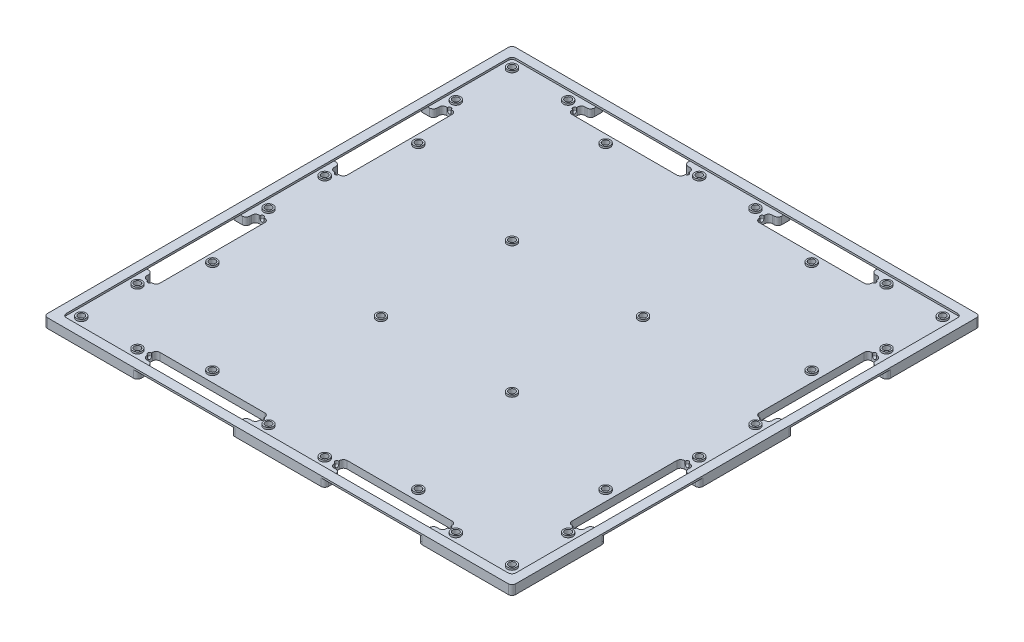
SolidWorks part; units mm, degrees
material "99.5% Aluminum Oxide"
ref_plane "Front Plane" through (0, 0, 0) normal (0, 0, 1) x (1, 0, 0)
ref_plane "Top Plane" through (0, 0, 0) normal (0, 1, 0) x (1, 0, 0)
ref_plane "Right Plane" through (0, 0, 0) normal (1, 0, 0) x (0, 0, -1)
sketch "Sketch1" plane through (0, 0, 0) normal (0, 1, 0) x (1, 0, 0)
  line L1 (-125, -125) -> (125, -125)
  line L2 (-125, -125) -> (-125, 125)
  line L3 (-125, 125) -> (125, 125)
  line L4 (125, -125) -> (125, 125)
  line L5 (-125, -125) -> (125, 125) construction
  line L6 (-125, 125) -> (125, -125) construction
  point P0 (0, 0)
  dimension "D1" = 250
extrude "Boss-Extrude1" add sketch "Sketch1" along normal mid plane 4
sketch "Sketch2" plane through (0, 2, 0) normal (0, 1, 0) x (1, 0, 0)
  line L0 (-125, 125) -> (-125, -125) construction
  line L1 (-120, -120) -> (120, -120)
  line L2 (-120, -120) -> (-120, 120)
  line L3 (-120, 120) -> (120, 120)
  line L4 (120, -120) -> (120, 120)
  line L5 (-120, -120) -> (120, 120) construction
  line L6 (-120, 120) -> (120, -120) construction
  point P0 (0, 0)
  dimension "D1" = 5
extrude "Cut-Extrude1" cut sketch "Sketch2" against normal blind 1
sketch "Sketch9" plane through (0, 1, 0) normal (0, 1, 0) x (1, 0, 0)
  line L0 (125, 125) -> (75, 125) construction
  line L1 (125, 125) -> (-125, 125) construction
  line L2 (25, 125) -> (-25, 125) construction
  line L3 (-125, 125) -> (-75, 125) construction
  line L4 (75, 117) -> (80, 117)
  line L5 (75, 125) -> (25, 125)
  line L6 (75, 125) -> (75, 117)
  line L8 (25, 125) -> (25, 117)
  line L9 (-25, 125) -> (-75, 125)
  line L10 (-25, 125) -> (-25, 117)
  line L12 (-75, 125) -> (-75, 117)
  line L13 (125, -125) -> (125, 125) construction
  line L32 (80, 117) -> (80, 110)
  line L33 (80, 110) -> (20, 110)
  line L34 (20, 110) -> (20, 117)
  line L35 (20, 117) -> (25, 117)
  line L36 (-25, 117) -> (-20, 117)
  line L37 (-20, 117) -> (-20, 110)
  line L38 (-20, 110) -> (-80, 110)
  line L39 (-80, 110) -> (-80, 117)
  line L40 (-80, 117) -> (-75, 117)
  dimension "D1" = 50
  dimension "D2" = 50
  dimension "D3" = 5
  dimension "D4" = 7
  dimension "D5" = 15
extrude "Cut-Extrude2" cut sketch "Sketch9" against normal through all
sketch "Sketch12" plane through (80, 0, 0) normal (-1, 0, 0) x (0, 0, 1)
  line L0 (-113.5, 1) -> (-113.5, -1.5)
  line L1 (-110, 1) -> (-117, 1) construction
  line L2 (-112.5, -0.5) -> (-112.5, 1)
  line L3 (-112.5, 1) -> (-113.5, 1)
  line L4 (-113.5, 1) -> (-113.5, -2) construction
  line L5 (-110, -2) -> (-117, -2) construction
  arc A0 (-113.5, -1.5) -> (-112.5, -0.5) centre (-113.5, -0.5) ccw
  point P7 (-113.5, -0.5)
  dimension "D1" = 1
revolve "Cut-Revolve1" cut sketch "Sketch12" angle 360 about L4
ref_plane "Plane1" through (50, 0, 0) normal (1, 0, 0) x (0, 0, -1)
mirror "Mirror1" about plane through (50, 0, 0) normal (1, 0, 0) of "Cut-Revolve1"
mirror "Mirror2" about plane through (0, 0, 0) normal (1, 0, 0) of "Cut-Revolve1", "Mirror1"
ref_axis "Center_Axis" through (0, -22.0017, 0) along (0, 1, 0)
pattern_circular "CirPattern1" count 4 over 360 about axis through (0, -22.0017, 0) along (0, 1, 0) of "Mirror2", "Cut-Extrude2", "Cut-Revolve1", "Mirror1"
sketch "Sketch14" plane through (0, 1, 0) normal (0, 1, 0) x (1, 0, 0)
  line L0 (-120, 120) -> (-120, -120) construction
  line L1 (-110, 120) -> (-110, -120) construction
  line L2 (-100, 120) -> (-100, -120) construction
  line L3 (-90, 120) -> (-90, -120) construction
  line L4 (-80, 120) -> (-80, -120) construction
  line L5 (-70, 120) -> (-70, -120) construction
  line L6 (-60, 120) -> (-60, -120) construction
  line L7 (-50, 120) -> (-50, -120) construction
  line L8 (-40, 120) -> (-40, -120) construction
  line L9 (-30, 120) -> (-30, -120) construction
  line L10 (-20, 120) -> (-20, -120) construction
  line L11 (-10, 120) -> (-10, -120) construction
  line L12 (0, 120) -> (0, -120) construction
  line L13 (10, 120) -> (10, -120) construction
  line L14 (20, 120) -> (20, -120) construction
  line L15 (30, 120) -> (30, -120) construction
  line L16 (40, 120) -> (40, -120) construction
  line L17 (50, 120) -> (50, -120) construction
  line L18 (60, 120) -> (60, -120) construction
  line L19 (70, 120) -> (70, -120) construction
  line L20 (80, 120) -> (80, -120) construction
  line L21 (90, 120) -> (90, -120) construction
  line L22 (100, 120) -> (100, -120) construction
  line L23 (110, 120) -> (110, -120) construction
  line L24 (120, 120) -> (120, -120) construction
  line L25 (-120, 120) -> (-110, 120) construction
  line L26 (-15, -115) -> (-15, -120) construction
  line L27 (-25, -120) -> (25, -120) construction
  line L28 (-125, 125) -> (-125, -125) construction
  line L29 (-85, -120) -> (-85, -115) construction
  line L30 (-120, -120) -> (-75, -120) construction
  line L31 (-115, -120) -> (-115, -115) construction
  line L32 (-120, -120) -> (120, -120) construction
  line L33 (-55, -110) -> (-55, -105) construction
  line L34 (-20, -110) -> (-80, -110) construction
  line L35 (-125, -125) -> (125, -125) construction
  line L36 (0, 0) -> (15, -115) construction
  line L37 (35, 35) -> (-35, 35) construction
  line L38 (35, 35) -> (35, -35) construction
  line L39 (35, -35) -> (-35, -35) construction
  line L40 (-35, 35) -> (-35, -35) construction
  line L41 (35, 35) -> (-35, -35) construction
  line L42 (35, -35) -> (-35, 35) construction
  line L43 (115, -117.5) -> (115, -120) construction
  line L44 (75, -120) -> (120, -120) construction
  circle A2 centre (-15, -115) radius 2.5
  circle A3 centre (-85, -115) radius 2.5
  circle A4 centre (-115, -115) radius 2.5
  circle A5 centre (-55, -105) radius 2.5
  circle A6 centre (-35, 35) radius 2.5
  circle A7 centre (-35, -35) radius 2.5
  circle A8 centre (35, -35) radius 2.5
  circle A9 centre (35, 35) radius 2.5
  circle A10 centre (15, -115) radius 2.5
  circle A11 centre (55, -105) radius 2.5
  circle A12 centre (85, -115) radius 2.5
  circle A13 centre (-115, 115) radius 2.5
  circle A14 centre (-115, 85) radius 2.5
  circle A15 centre (-105, 55) radius 2.5
  circle A16 centre (-115, 15) radius 2.5
  circle A17 centre (-115, -15) radius 2.5
  circle A18 centre (-105, -55) radius 2.5
  circle A19 centre (-115, -85) radius 2.5
  circle A20 centre (115, 115) radius 2.5
  circle A21 centre (85, 115) radius 2.5
  circle A22 centre (55, 105) radius 2.5
  circle A23 centre (15, 115) radius 2.5
  circle A24 centre (-15, 115) radius 2.5
  circle A25 centre (-55, 105) radius 2.5
  circle A26 centre (-85, 115) radius 2.5
  circle A27 centre (115, -115) radius 2.5
  circle A28 centre (115, -85) radius 2.5
  circle A29 centre (105, -55) radius 2.5
  circle A30 centre (115, -15) radius 2.5
  circle A31 centre (115, 15) radius 2.5
  circle A32 centre (105, 55) radius 2.5
  circle A33 centre (115, 85) radius 2.5
  arc A34 (120, -118) -> (118, -120) centre (118, -118) cw construction
  point P78 (0, 0)
  dimension "D5" = 5
  dimension "D14" = 2
  dimension "D2" = 10
  dimension "D3" = 110
  dimension "D4" = 5
  dimension "D6" = 40
  dimension "D7" = 10
  dimension "D8" = 20
  dimension "D9" = 70
  dimension "D10" = 90
  dimension "D12" = 115.9741
  dimension "D13" = 2.5
  dimension "D1" = 25
  dimension "D11" = 4
extrude "Boss-Extrude2" add sketch "Sketch14" along normal up to surface (1 mm away) up to face at (0, 2, 0)
sketch "Sketch19" plane through (0, -2, 0) normal (0, -1, 0) x (1, 0, 0)
  line L0 (-110, 55) -> (-105, 55) construction
  line L1 (-100, -100) -> (100, -100)
  line L2 (-100, -100) -> (-100, 100)
  line L3 (-100, 100) -> (100, 100)
  line L4 (100, -100) -> (100, 100)
  line L5 (-100, -100) -> (100, 100) construction
  line L6 (-100, 100) -> (100, -100) construction
  line L7 (-105, 55) -> (-100, 55) construction
  line L68 (117, -25) -> (125, -25)
  line L69 (125, -25) -> (125, 25)
  line L70 (125, 25) -> (117, 25)
  line L71 (117, 25) -> (117, 20)
  line L72 (117, 20) -> (110, 20)
  line L73 (110, 20) -> (110, 80)
  line L74 (110, 80) -> (117, 80)
  line L75 (117, 80) -> (117, 75)
  line L76 (117, 75) -> (125, 75)
  line L77 (125, 75) -> (125, 125)
  line L78 (125, 125) -> (75, 125)
  line L79 (75, 125) -> (75, 117)
  line L80 (75, 117) -> (80, 117)
  line L81 (80, 117) -> (80, 110)
  line L82 (80, 110) -> (20, 110)
  line L83 (20, 110) -> (20, 117)
  line L84 (20, 117) -> (25, 117)
  line L85 (25, 117) -> (25, 125)
  line L86 (25, 125) -> (-25, 125)
  line L87 (-25, 125) -> (-25, 117)
  line L88 (-25, 117) -> (-20, 117)
  line L89 (-20, 117) -> (-20, 110)
  line L90 (-20, 110) -> (-80, 110)
  line L91 (-80, 110) -> (-80, 117)
  line L92 (-80, 117) -> (-75, 117)
  line L93 (-75, 117) -> (-75, 125)
  line L94 (-75, 125) -> (-125, 125)
  line L95 (-125, 125) -> (-125, 75)
  line L96 (-125, 75) -> (-117, 75)
  line L97 (-117, 75) -> (-117, 80)
  line L98 (-117, 80) -> (-110, 80)
  line L99 (-110, 80) -> (-110, 20)
  line L100 (-110, 20) -> (-117, 20)
  line L101 (-117, 20) -> (-117, 25)
  line L102 (-117, 25) -> (-125, 25)
  line L103 (-125, 25) -> (-125, -25)
  line L104 (-125, -25) -> (-117, -25)
  line L105 (-117, -25) -> (-117, -20)
  line L106 (-117, -20) -> (-110, -20)
  line L107 (-110, -20) -> (-110, -80)
  line L108 (-110, -80) -> (-117, -80)
  line L109 (-117, -80) -> (-117, -75)
  line L110 (-117, -75) -> (-125, -75)
  line L111 (-125, -75) -> (-125, -125)
  line L112 (-125, -125) -> (-75, -125)
  line L113 (-75, -125) -> (-75, -117)
  line L114 (-75, -117) -> (-80, -117)
  line L115 (-80, -117) -> (-80, -110)
  line L116 (-80, -110) -> (-20, -110)
  line L117 (-20, -110) -> (-20, -117)
  line L118 (-20, -117) -> (-25, -117)
  line L119 (-25, -117) -> (-25, -125)
  line L120 (-25, -125) -> (25, -125)
  line L121 (25, -125) -> (25, -117)
  line L122 (25, -117) -> (20, -117)
  line L123 (20, -117) -> (20, -110)
  line L124 (20, -110) -> (80, -110)
  line L125 (80, -110) -> (80, -117)
  line L126 (80, -117) -> (75, -117)
  line L127 (75, -117) -> (75, -125)
  line L128 (75, -125) -> (125, -125)
  line L129 (125, -125) -> (125, -75)
  line L130 (125, -75) -> (117, -75)
  line L131 (117, -75) -> (117, -80)
  line L132 (117, -80) -> (110, -80)
  line L133 (110, -80) -> (110, -20)
  line L134 (110, -20) -> (117, -20)
  line L135 (117, -20) -> (117, -25)
  line L136 (117, -25) -> (125, -25)
  line L137 (125, -25) -> (125, 25)
  line L138 (125, 25) -> (117, 25)
  line L139 (117, 25) -> (117, 20)
  line L140 (117, 20) -> (110, 20)
  line L141 (110, 20) -> (110, 80)
  line L142 (110, 80) -> (117, 80)
  line L143 (117, 80) -> (117, 75)
  line L144 (117, 75) -> (125, 75)
  line L145 (125, 75) -> (125, 125)
  line L146 (125, 125) -> (75, 125)
  line L147 (75, 125) -> (75, 117)
  line L148 (75, 117) -> (80, 117)
  line L149 (80, 117) -> (80, 110)
  line L150 (80, 110) -> (20, 110)
  line L151 (20, 110) -> (20, 117)
  line L152 (20, 117) -> (25, 117)
  line L153 (25, 117) -> (25, 125)
  line L154 (25, 125) -> (-25, 125)
  line L155 (-25, 125) -> (-25, 117)
  line L156 (-25, 117) -> (-20, 117)
  line L157 (-20, 117) -> (-20, 110)
  line L158 (-20, 110) -> (-80, 110)
  line L159 (-80, 110) -> (-80, 117)
  line L160 (-80, 117) -> (-75, 117)
  line L161 (-75, 117) -> (-75, 125)
  line L162 (-75, 125) -> (-125, 125)
  line L163 (-125, 125) -> (-125, 75)
  line L164 (-125, 75) -> (-117, 75)
  line L165 (-117, 75) -> (-117, 80)
  line L166 (-117, 80) -> (-110, 80)
  line L167 (-110, 80) -> (-110, 20)
  line L168 (-110, 20) -> (-117, 20)
  line L169 (-117, 20) -> (-117, 25)
  line L170 (-117, 25) -> (-125, 25)
  line L171 (-125, 25) -> (-125, -25)
  line L172 (-125, -25) -> (-117, -25)
  line L173 (-117, -25) -> (-117, -20)
  line L174 (-117, -20) -> (-110, -20)
  line L175 (-110, -20) -> (-110, -80)
  line L176 (-110, -80) -> (-117, -80)
  line L177 (-117, -80) -> (-117, -75)
  line L178 (-117, -75) -> (-125, -75)
  line L179 (-125, -75) -> (-125, -125)
  line L180 (-125, -125) -> (-75, -125)
  line L181 (-75, -125) -> (-75, -117)
  line L182 (-75, -117) -> (-80, -117)
  line L183 (-80, -117) -> (-80, -110)
  line L184 (-80, -110) -> (-20, -110)
  line L185 (-20, -110) -> (-20, -117)
  line L186 (-20, -117) -> (-25, -117)
  line L187 (-25, -117) -> (-25, -125)
  line L188 (-25, -125) -> (25, -125)
  line L189 (25, -125) -> (25, -117)
  line L190 (25, -117) -> (20, -117)
  line L191 (20, -117) -> (20, -110)
  line L192 (20, -110) -> (80, -110)
  line L193 (80, -110) -> (80, -117)
  line L194 (80, -117) -> (75, -117)
  line L195 (75, -117) -> (75, -125)
  line L196 (75, -125) -> (125, -125)
  line L197 (125, -125) -> (125, -75)
  line L198 (125, -75) -> (117, -75)
  line L199 (117, -75) -> (117, -80)
  line L200 (117, -80) -> (110, -80)
  line L201 (110, -80) -> (110, -20)
  line L202 (110, -20) -> (117, -20)
  line L203 (117, -20) -> (117, -25)
  circle A1 centre (-105, 55) radius 2.5
  circle A2 centre (-105, 55) radius 2.5 construction
  point P2 (0, 0)
  dimension "D3" = 10
  dimension "D1" = 0
  dimension "D2" = 0
extrude "Boss-Extrude3" add sketch "Sketch19" along normal blind 1
sketch "Sketch20" plane through (0, -2, 0) normal (0, -1, 0) x (1, 0, 0)
  line L0 (33.3771, -47.8109) -> (58.094, -5)
  line L37 (-49.4338, 0) -> (-24.7169, -42.8109)
  line L38 (-24.7169, -42.8109) -> (24.7169, -42.8109)
  line L39 (24.7169, -42.8109) -> (49.4338, 0)
  line L40 (49.4338, 0) -> (24.7169, 42.8109)
  line L41 (24.7169, 42.8109) -> (-24.7169, 42.8109)
  line L42 (-24.7169, 42.8109) -> (-49.4338, 0)
  line L43 (58.094, -5) -> (100, -5)
  line L44 (100, -100) -> (100, 100) construction
  line L45 (33.3771, -47.8109) -> (63.5085, -100)
  line L46 (-100, -100) -> (100, -100) construction
  line L47 (100, -100) -> (100, 100) construction
  line L48 (-100, -100) -> (100, -100) construction
  line L49 (49.4338, 0) -> (-49950.5662, 0) construction
  line L50 (51.9615, -100) -> (24.7169, -52.8109)
  line L51 (24.7169, -52.8109) -> (-24.7169, -52.8109)
  line L53 (-24.7169, -52.8109) -> (-51.9615, -100)
  line L54 (0, 0) -> (0, -50000) construction
  line L55 (-33.3771, -47.8109) -> (-63.5085, -100)
  line L56 (-33.3771, -47.8109) -> (-58.094, -5)
  line L57 (-58.094, -5) -> (-100, -5)
  line L58 (-33.3771, 47.8109) -> (-63.5085, 100)
  line L59 (-58.094, 5) -> (-100, 5)
  line L60 (-33.3771, 47.8109) -> (-58.094, 5)
  line L61 (24.7169, 52.8109) -> (-24.7169, 52.8109)
  line L62 (-24.7169, 52.8109) -> (-51.9615, 100)
  line L63 (51.9615, 100) -> (24.7169, 52.8109)
  line L64 (33.3771, 47.8109) -> (63.5085, 100)
  line L65 (33.3771, 47.8109) -> (58.094, 5)
  line L66 (58.094, 5) -> (100, 5)
  line L67 (63.5085, -100) -> (51.9615, -100)
  line L68 (-51.9615, -100) -> (-63.5085, -100)
  line L69 (-100, -5) -> (-100, 5)
  line L70 (-63.5085, 100) -> (-51.9615, 100)
  line L71 (51.9615, 100) -> (63.5085, 100)
  line L72 (100, -5) -> (100, 5)
  circle A0 centre (35, -35) radius 2.5 construction
  circle A1 centre (35, 35) radius 2.5 construction
  circle A2 centre (-35, -35) radius 2.5 construction
  circle A3 centre (-35, 35) radius 2.5 construction
  circle A4 centre (35, -35) radius 2.5 construction
  circle A5 centre (35, 35) radius 2.5 construction
  circle A6 centre (-35, -35) radius 2.5 construction
  circle A7 centre (-35, 35) radius 2.5 construction
  circle A8 centre (0, 0) radius 42.8109 construction
  arc A9 (100, -8.6024) -> (100, -87.0194) centre (82.8109, -47.8109) ccw construction
  arc A10 (42.5864, -100) -> (-42.5864, -100) centre (0, -95.6218) ccw construction
  dimension "D1" = 5
  dimension "D2" = 5
  dimension "D3" = 5
  dimension "D4" = 10
extrude "Boss-Extrude4" add sketch "Sketch20" along normal up to surface (1 mm away) up to face at (0, -3, 0)
sketch "Sketch24" plane through (0, -3, 0) normal (0, -1, 0) x (1, 0, 0)
  circle A0 centre (-105, 55) radius 2.5 construction
  circle A1 centre (-115, 85) radius 2.5 construction
  circle A2 centre (-115, 115) radius 2.5 construction
  circle A3 centre (-85, 115) radius 2.5 construction
  circle A4 centre (-115, -15) radius 2.5 construction
  circle A5 centre (-115, -85) radius 2.5 construction
  circle A6 centre (-55, -105) radius 2.5 construction
  circle A7 centre (15, -115) radius 2.5 construction
  circle A8 centre (55, -105) radius 2.5 construction
  circle A9 centre (85, -115) radius 2.5 construction
  circle A10 centre (115, -85) radius 2.5 construction
  circle A11 centre (105, -55) radius 2.5 construction
  circle A12 centre (-55, 105) radius 2.5 construction
  circle A13 centre (-115, 15) radius 2.5 construction
  circle A14 centre (-35, 35) radius 2.5 construction
  circle A15 centre (35, -35) radius 2.5 construction
  circle A16 centre (-35, -35) radius 2.5 construction
  circle A17 centre (-105, -55) radius 2.5 construction
  circle A18 centre (-115, -115) radius 2.5 construction
  circle A19 centre (-85, -115) radius 2.5 construction
  circle A20 centre (-15, -115) radius 2.5 construction
  circle A21 centre (115, -115) radius 2.5 construction
  circle A22 centre (115, -15) radius 2.5 construction
  circle A23 centre (115, 15) radius 2.5 construction
  circle A24 centre (105, 55) radius 2.5 construction
  circle A25 centre (35, 35) radius 2.5 construction
  circle A26 centre (-15, 115) radius 2.5 construction
  circle A27 centre (15, 115) radius 2.5 construction
  circle A28 centre (55, 105) radius 2.5 construction
  circle A29 centre (85, 115) radius 2.5 construction
  circle A30 centre (115, 85) radius 2.5 construction
  circle A31 centre (115, 115) radius 2.5 construction
  circle A32 centre (-105, 55) radius 2.5 construction
  circle A33 centre (-115, 85) radius 2.5 construction
  circle A34 centre (-115, 115) radius 2.5 construction
  circle A35 centre (-85, 115) radius 2.5 construction
  circle A36 centre (-115, -15) radius 2.5 construction
  circle A37 centre (-115, -85) radius 2.5 construction
  circle A38 centre (-55, -105) radius 2.5 construction
  circle A39 centre (15, -115) radius 2.5 construction
  circle A40 centre (55, -105) radius 2.5 construction
  circle A41 centre (85, -115) radius 2.5 construction
  circle A42 centre (115, -85) radius 2.5 construction
  circle A43 centre (105, -55) radius 2.5 construction
  circle A44 centre (-55, 105) radius 2.5 construction
  circle A45 centre (-115, 15) radius 2.5 construction
  circle A46 centre (-35, 35) radius 2.5 construction
  circle A47 centre (35, -35) radius 2.5 construction
  circle A48 centre (-35, -35) radius 2.5 construction
  circle A49 centre (-105, -55) radius 2.5 construction
  circle A50 centre (-115, -115) radius 2.5 construction
  circle A51 centre (-85, -115) radius 2.5 construction
  circle A52 centre (-15, -115) radius 2.5 construction
  circle A53 centre (115, -115) radius 2.5 construction
  circle A54 centre (115, -15) radius 2.5 construction
  circle A55 centre (115, 15) radius 2.5 construction
  circle A56 centre (105, 55) radius 2.5 construction
  circle A57 centre (35, 35) radius 2.5 construction
  circle A58 centre (-15, 115) radius 2.5 construction
  circle A59 centre (15, 115) radius 2.5 construction
  circle A60 centre (55, 105) radius 2.5 construction
  circle A61 centre (85, 115) radius 2.5 construction
  circle A62 centre (115, 85) radius 2.5 construction
  circle A63 centre (115, 115) radius 2.5 construction
hole_wizard "CBORE for M3 SBHCS2" positions "3DSketch3" profile "Sketch26" counterbore size "M3" standard "ANSI Metric" end condition through all
sketch3d "3DSketch3"
  point P0 (-115, -3, 115)
  point P3 (-115, -3, 85)
  point P6 (-105, -3, 55)
  point P9 (-85, -3, 115)
  point P12 (-55, -3, 105)
  point P15 (-15, -3, 115)
  point P18 (15, -3, 115)
  point P21 (55, -3, 105)
  point P24 (85, -3, 115)
  point P27 (115, -3, 115)
  point P30 (115, -3, 85)
  point P33 (105, -3, 55)
  point P36 (35, -3, 35)
  point P39 (-35, -3, 35)
  point P42 (-115, -3, 15)
  point P45 (-115, -3, -15)
  point P48 (-105, -3, -55)
  point P51 (-115, -3, -85)
  point P54 (-115, -3, -115)
  point P57 (-85, -3, -115)
  point P60 (-55, -3, -105)
  point P63 (-15, -3, -115)
  point P66 (15, -3, -115)
  point P69 (55, -3, -105)
  point P72 (85, -3, -115)
  point P75 (115, -3, -115)
  point P78 (115, -3, -85)
  point P81 (105, -3, -55)
  point P84 (115, -3, -15)
  point P87 (115, -3, 15)
  point P90 (35, -3, -35)
  point P93 (-35, -3, -35)
sketch "Sketch26" plane through (-115, -3, 115) normal (1, 0, 0) x (0, 0, -1)
  line L0 (0, 0) -> (0, 5)
  line L1 (0, 5) -> (1.7, 5)
  line L3 (1.7, 5) -> (1.7, 1)
  line L4 (1.7, 1) -> (2.75, 1)
  line L5 (2.75, 1) -> (2.75, 0)
  line L7 (2.75, 0) -> (0, 0)
  line L11 (0, -6.35) -> (0, 107.95) construction
  dimension "Thru Hole Dia." = 3.4
  dimension "Thru Hole Depth" = 5
  dimension "C'Bore Dia." = 5.5
  dimension "C'Bore Depth" = 1
fillet "Fillet2" radius 2 72 edges at (-120, 1.5, -120) (-120, 1.5, 120) (120, 1.5, -120) (120, 1.5, 120) (117, -1, -20) (110, -1, -20) (110, -1, -80) (117, -1, -80) (117, -1, -75) (125, -1, -75) (125, -0.5, -125) (75, -1, -125) (75, -1, -117) (80, -1, -117) (80, -1, -110) (20, -1, -110) (20, -1, -117) (25, -1, -117) (25, -1, -125) (-25, -1, -125) (-25, -1, -117) (-20, -1, -117) (-20, -1, -110) (-80, -1, -110) (-80, -1, -117) (-75, -1, -117) (-75, -1, -125) (-125, -0.5, -125) (-125, -1, -75) (-117, -1, -75) (-117, -1, -80) (-110, -1, -80) (-110, -1, -20) (-117, -1, -20) (-117, -1, -25) (-125, -1, -25) (-125, -1, 25) (-117, -1, 25) (-117, -1, 20) (-110, -1, 20) (-110, -1, 80) (-117, -1, 80) (-117, -1, 75) (-125, -1, 75) (-125, -0.5, 125) (-75, -1, 125) (-75, -1, 117) (-80, -1, 117) (-80, -1, 110) (-20, -1, 110) (-20, -1, 117) (-25, -1, 117) (-25, -1, 125) (25, -1, 125) (25, -1, 117) (20, -1, 117) (20, -1, 110) (80, -1, 110) (80, -1, 117) (75, -1, 117) (75, -1, 125) (125, -0.5, 125) (125, -1, 75) (117, -1, 80) (110, -1, 80) (110, -1, 20) (117, -1, 20) (117, -1, 25) (125, -1, 25) (125, -1, -25) (117, -1, -25) (117, -1, 75)
fillet "Fillet3" radius 10 34 edges at (-49.4338, -2.5, 0) (-24.7169, -2.5, -42.8109) (24.7169, -2.5, -42.8109) (49.4338, -2.5, 0) (24.7169, -2.5, 42.8109) (-24.7169, -2.5, 42.8109) (58.094, -2.5, -5) (33.3771, -2.5, -47.8109) (63.5085, -2.5, -100) (100, -2.5, -100) (100, -2.5, -5) (51.9615, -2.5, -100) (24.7169, -2.5, -52.8109) (-24.7169, -2.5, -52.8109) (-51.9615, -2.5, -100) (-100, -2.5, -100) (-63.5085, -2.5, -100) (-33.3771, -2.5, -47.8109) (-58.094, -2.5, -5) (-100, -2.5, -5) (-100, -2.5, 5) (-58.094, -2.5, 5) (-51.9615, -2.5, 100) (-24.7169, -2.5, 52.8109) (24.7169, -2.5, 52.8109) (51.9615, -2.5, 100) (100, -2.5, 100) (63.5085, -2.5, 100) (33.3771, -2.5, 47.8109) (58.094, -2.5, 5) (100, -2.5, 5) (-33.3771, -2.5, 47.8109) (-63.5085, -2.5, 100) (-100, -2.5, 100)
